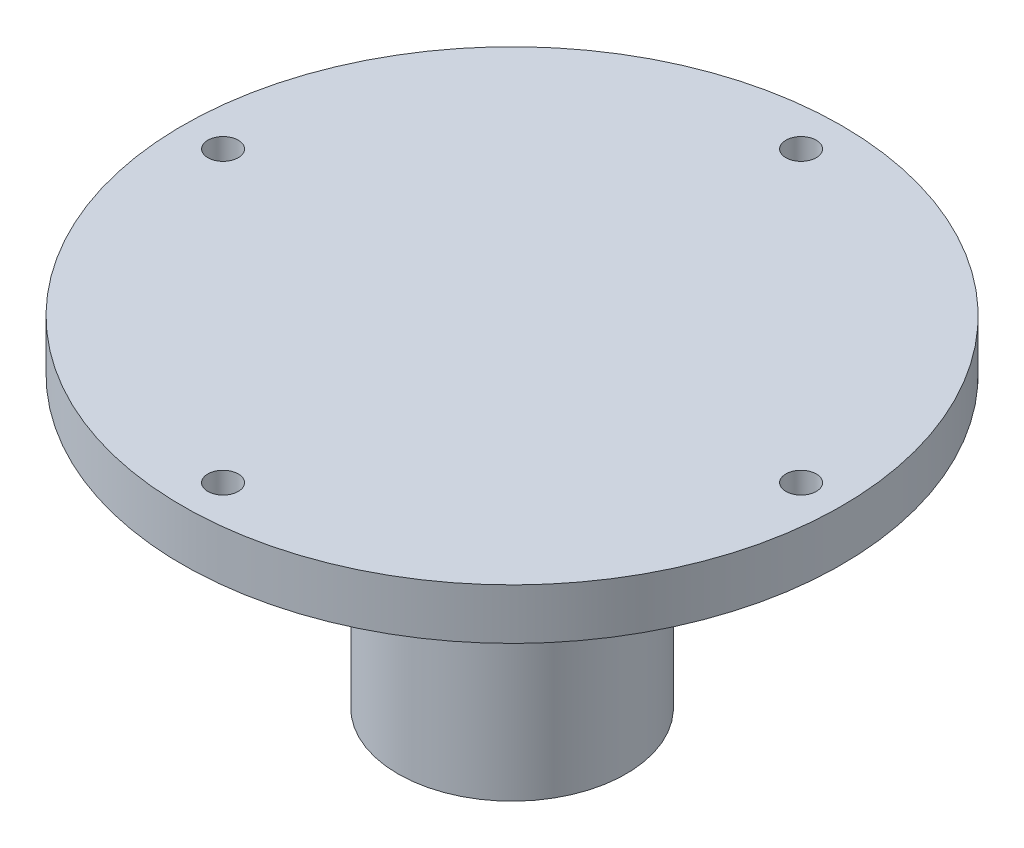
SolidWorks part; units mm, degrees
ref_plane "Front Plane" through (0, 0, 0) normal (0, 0, 1) x (1, 0, 0)
ref_plane "Top Plane" through (0, 0, 0) normal (0, 1, 0) x (1, 0, 0)
ref_plane "Right Plane" through (0, 0, 0) normal (1, 0, 0) x (0, 0, -1)
sketch "Sketch1" plane through (0, 0, 0) normal (1, 0, 0) x (0, 0, -1)
  line L0 (0, 0) -> (0, -47)
  line L1 (0, -47) -> (22.5, -47)
  line L2 (22.5, -47) -> (22.5, 0)
  line L3 (22.5, 0) -> (50, 0)
  line L4 (50, 0) -> (50, 20)
  line L5 (50, 20) -> (0, 20)
  line L6 (0, 20) -> (0, 0)
  dimension "D1" = 22.5
  dimension "D2" = 50
  dimension "D3" = 20
  dimension "D4" = 47
revolve "Revolve1" add sketch "Sketch1" angle 360 about L6
sketch "Sketch2" plane through (0, 0, 0) normal (0, 1, 0) x (1, 0, 0)
  line L0 (0, 0) -> (0, -57) construction
  line L1 (57, 0) -> (0, 0) construction
  line L2 (0, 0) -> (0, 57) construction
  line L3 (0, 0) -> (-57, 0) construction
  circle A0 centre (0, 0) radius 65
  circle A1 centre (0, -57) radius 3
  circle A2 centre (57, 0) radius 3
  circle A3 centre (0, 57) radius 3
  circle A4 centre (-57, 0) radius 3
  dimension "D1" = 6
  dimension "D3" = 130
  dimension "D2" = 57
extrude "Boss-Extrude1" add sketch "Sketch2" against normal blind 10 from surface starting at face at (0, 20, 50)
